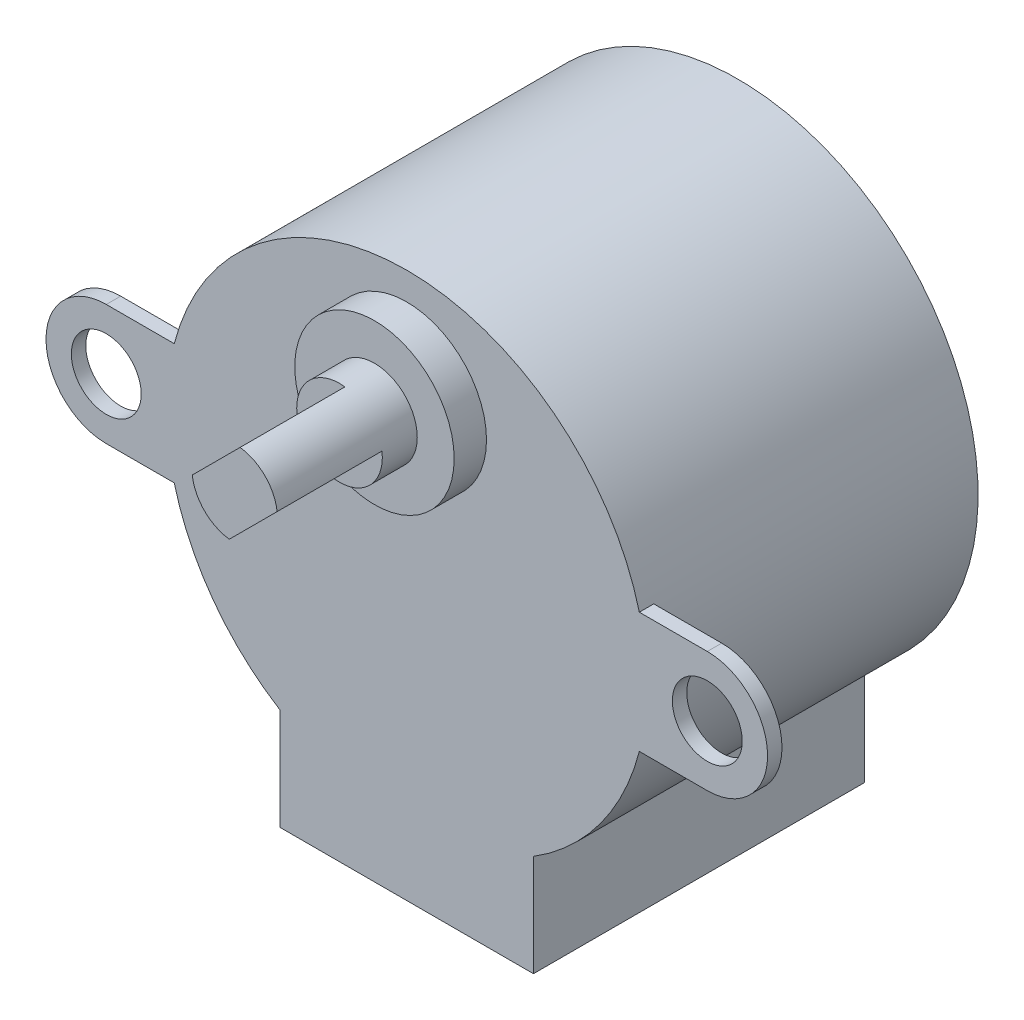
SolidWorks part; units mm, degrees
ref_plane "Front Plane" through (0, 0, 0) normal (0, 0, 1) x (1, 0, 0)
ref_plane "Top Plane" through (0, 0, 0) normal (0, 1, 0) x (1, 0, 0)
ref_plane "Right Plane" through (0, 0, 0) normal (1, 0, 0) x (0, 0, -1)
sketch "Sketch1" plane through (0, 0, 0) normal (0, 0, 1) x (1, 0, 0)
  line L0 (-7.366, -17.78) -> (7.366, -17.78)
  line L3 (-7.366, -11.8703) -> (-7.366, -17.78)
  line L5 (7.366, -11.8703) -> (7.366, -17.78)
  arc A0 (7.366, -11.8703) -> (-7.366, -11.8703) centre (0, 0) ccw
  dimension "D1" = 27.94
  dimension "D2" = 3.81
extrude "Boss-Extrude1" add sketch "Sketch1" along normal blind 19.2532
sketch "Sketch2" plane through (0, 0, 19.2532) normal (0, 0, 1) x (1, 0, 0)
  line L0 (0, 0) -> (12.5609, 0) construction
  line L1 (0, 0) -> (0, 9.396) construction
  line L3 (-13.5231, -3.5052) -> (-17.4752, -3.5052)
  line L5 (-13.5231, 3.5052) -> (-17.4752, 3.5052)
  line L7 (13.5231, 3.5052) -> (17.4752, 3.5052)
  line L8 (13.5231, -3.5052) -> (17.4752, -3.5052)
  arc A0 (-17.4752, 3.5052) -> (-17.4752, -3.5052) centre (-17.4752, 0) ccw
  arc A1 (-13.5231, 3.5052) -> (-13.5231, -3.5052) centre (0, 0) ccw
  circle A3 centre (-17.4752, 0) radius 2.032
  circle A4 centre (17.4752, 0) radius 2.032
  arc A5 (13.5231, 3.5052) -> (13.5231, -3.5052) centre (0, 0) cw
  arc A6 (17.4752, 3.5052) -> (17.4752, -3.5052) centre (17.4752, 0) cw
  point P3 (-13.97, 0)
  point P6 (-20.9804, 0)
  dimension "D2" = 4.064
  dimension "D1" = 7.0104
extrude "Boss-Extrude2" add sketch "Sketch2" against normal blind 0.8382
sketch "Sketch3" plane through (0, 0, 19.2532) normal (0, 0, 1) x (1, 0, 0)
  circle A0 centre (0, 7.7343) radius 4.6355
  arc A1 (13.5231, 3.5052) -> (-13.5231, 3.5052) centre (0, 0) ccw construction
  point P5 (0, 13.97)
  dimension "D1" = 9.271
  dimension "D2" = 1.6002
extrude "Boss-Extrude3" add sketch "Sketch3" along normal blind 1.8796
sketch "Sketch4" plane through (0, 0, 21.1328) normal (0, 0, 1) x (1, 0, 0)
  circle A0 centre (0, 7.7343) radius 2.4892
  dimension "D1" = 4.9784
extrude "Boss-Extrude4" add sketch "Sketch4" along normal blind 8.128
sketch "Sketch5" plane through (0, 0, 29.2608) normal (0, 0, 1) x (1, 0, 0)
  line L7 (2.4693, 8.0483) -> (-0.314, 5.265)
  line L9 (0, 7.7343) -> (1.4085, 9.1428) construction
  line L10 (0.314, 10.2036) -> (-2.4693, 7.4203)
  arc A6 (-0.314, 5.265) -> (2.4693, 8.0483) centre (0, 7.7343) ccw
  arc A7 (-2.4693, 7.4203) -> (0.314, 10.2036) centre (0, 7.7343) cw
  point P0 (0, 7.7343)
  dimension "D1" = 1.524
extrude "Cut-Extrude1" cut sketch "Sketch5" against normal blind 6.096
sketch "Sketch6" plane through (0, 0, 29.2608) normal (0, 0, 1) x (1, 0, 0)
  point P0 (0, 7.7343)
